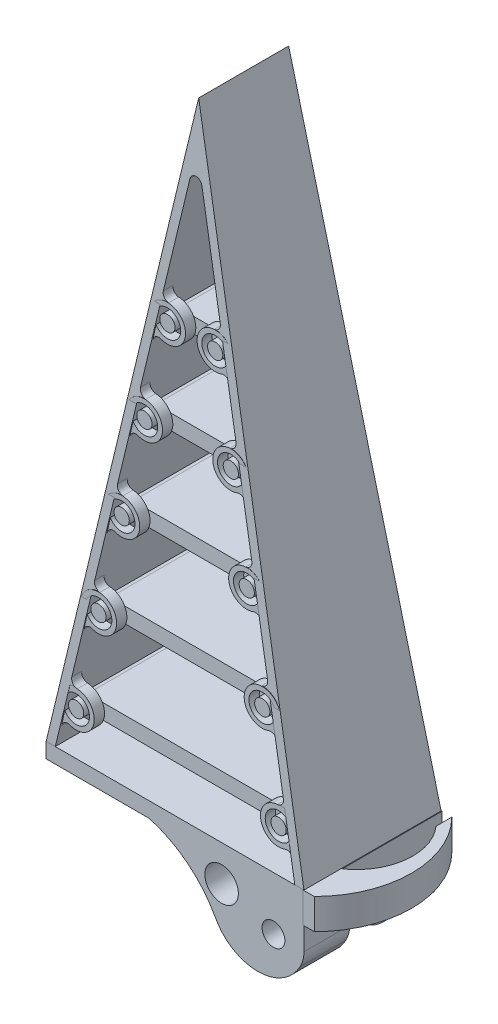
SolidWorks part; units mm, degrees
ref_plane "Ebene vorne" through (0, 0, 0) normal (0, 0, 1) x (1, 0, 0)
ref_plane "Ebene oben" through (0, 0, 0) normal (0, 1, 0) x (1, 0, 0)
ref_plane "Ebene rechts" through (0, 0, 0) normal (1, 0, 0) x (0, 0, -1)
ref_plane "Ebene7" through (0, 0, 9) normal (0, 0, 1) x (1, 0, 0)
ref_plane "Ebene8" through (17, 0, 0) normal (1, 0, 0) x (0, 0, -1)
sketch "Skizze1" plane through (0, 0, 0) normal (0, 0, 1) x (1, 0, 0)
  line L0 (0, 0) -> (16.9111, -80)
  line L1 (16.9111, -80) -> (15.7111, -80)
  line L2 (15.7111, -80) -> (0, -5.6767)
  line L3 (0, -5.6767) -> (-15.7111, -80)
  line L4 (-15.7111, -80) -> (-16.9111, -80)
  line L5 (-16.9111, -80) -> (0, 0)
  point P2 (-16.3111, -80)
  dimension "D1" = 1.2
  dimension "D2" = 1.2
  dimension "D3" = 23.872
  dimension "D4" = 80
extrude "Aufsatz-Linear austragen4" add sketch "Skizze1" along normal blind 18
sketch "Skizze11" plane through (17, 0, 0) normal (1, 0, 0) x (0, 0, -1)
  line L0 (-18, -80) -> (-14.9, 0)
  line L1 (-18, 0) -> (0, 0) construction
  line L2 (-14.9, 0) -> (-18, 0)
  line L3 (-18, 0) -> (-18, -80)
  line L4 (0, -80) -> (-3.1, 0)
  line L5 (-3.1, 0) -> (0, 0)
  line L6 (0, 0) -> (0, -80)
  dimension "D1" = 3.1
  dimension "D2" = 3.1
extrude "Schnitt-Linear austragen1" cut sketch "Skizze11" against normal through all
sketch "Skizze6" plane through (0, 0, 9) normal (0, 0, 1) x (1, 0, 0)
  line L1 (0, -5.6767) -> (-15.7111, -80) construction
  line L2 (15.7111, -80) -> (0, -5.6767) construction
  line L8 (3.1325, -25.6767) -> (-3.1325, -25.6767)
  line L11 (-3.1325, -27.6767) -> (3.1325, -27.6767)
  arc A0 (-3.1325, -25.6767) -> (-3.1325, -27.6767) centre (-3.1325, -26.6767) ccw
  arc A1 (3.1325, -25.6767) -> (3.1325, -27.6767) centre (3.1325, -26.6767) cw
  point P4 (-4.1325, -26.6767)
  point P9 (4.1325, -26.6767)
  dimension "D3" = 0.3
  dimension "D1" = 20
  dimension "D2" = 2
  dimension "D4" = 0.3
extrude "Aufsatz-Linear austragen5" add sketch "Skizze6" along normal blind 5.37 and the other way blind 5.37
sketch "Skizze7" plane through (0, 0, 9) normal (0, 0, 1) x (1, 0, 0)
  line L9 (5.6692, -37.6767) -> (-5.6692, -37.6767)
  line L12 (-5.6692, -39.6767) -> (5.6692, -39.6767)
  line L13 (-3.1325, -27.6767) -> (3.1325, -27.6767) construction
  line L14 (0, -5.6767) -> (-15.7111, -80) construction
  line L15 (15.7111, -80) -> (0, -5.6767) construction
  arc A0 (-5.6692, -37.6767) -> (-5.6692, -39.6767) centre (-5.6692, -38.6767) ccw
  arc A1 (5.6692, -37.6767) -> (5.6692, -39.6767) centre (5.6692, -38.6767) cw
  point P3 (-6.6692, -38.6767)
  point P10 (6.6692, -38.6767)
  dimension "D3" = 0.3
  dimension "D1" = 10
  dimension "D2" = 2
  dimension "D4" = 0.3
extrude "Aufsatz-Linear austragen6" add sketch "Skizze7" along normal blind 5.85 and the other way blind 5.85
sketch "Skizze8" plane through (0, 0, 9) normal (0, 0, 1) x (1, 0, 0)
  line L9 (8.2059, -49.6767) -> (-8.2059, -49.6767)
  line L12 (-8.2059, -51.6767) -> (8.2059, -51.6767)
  line L13 (-5.6692, -39.6767) -> (5.6692, -39.6767) construction
  line L14 (0, -5.6767) -> (-15.7111, -80) construction
  line L15 (15.7111, -80) -> (0, -5.6767) construction
  arc A0 (-8.2059, -49.6767) -> (-8.2059, -51.6767) centre (-8.2059, -50.6767) ccw
  arc A1 (8.2059, -49.6767) -> (8.2059, -51.6767) centre (8.2059, -50.6767) cw
  point P6 (-9.2059, -50.6767)
  point P11 (9.2059, -50.6767)
  dimension "D3" = 0.3
  dimension "D1" = 10
  dimension "D2" = 2
  dimension "D4" = 0.3
extrude "Aufsatz-Linear austragen7" add sketch "Skizze8" along normal blind 6.3 and the other way blind 6.3
sketch "Skizze9" plane through (0, 0, 9) normal (0, 0, 1) x (1, 0, 0)
  line L9 (10.7426, -61.6767) -> (-10.7426, -61.6767)
  line L12 (-10.7426, -63.6767) -> (10.7426, -63.6767)
  line L13 (-8.2059, -51.6767) -> (8.2059, -51.6767) construction
  line L14 (0, -5.6767) -> (-15.7111, -80) construction
  line L15 (15.7111, -80) -> (0, -5.6767) construction
  arc A0 (-10.7426, -61.6767) -> (-10.7426, -63.6767) centre (-10.7426, -62.6767) ccw
  arc A1 (10.7426, -61.6767) -> (10.7426, -63.6767) centre (10.7426, -62.6767) cw
  point P3 (-11.7426, -62.6767)
  point P10 (11.7426, -62.6767)
  dimension "D3" = 0.3
  dimension "D1" = 10
  dimension "D2" = 2
  dimension "D4" = 0.3
extrude "Aufsatz-Linear austragen8" add sketch "Skizze9" along normal blind 6.8 and the other way blind 6.8
sketch "Skizze10" plane through (0, 0, 9) normal (0, 0, 1) x (1, 0, 0)
  line L9 (13.2792, -73.6767) -> (-13.2792, -73.6767)
  line L12 (-13.2792, -75.6767) -> (13.2792, -75.6767)
  line L13 (-10.7426, -63.6767) -> (10.7426, -63.6767) construction
  line L14 (0, -5.6767) -> (-15.7111, -80) construction
  line L15 (15.7111, -80) -> (0, -5.6767) construction
  arc A0 (-13.2792, -73.6767) -> (-13.2792, -75.6767) centre (-13.2792, -74.6767) ccw
  arc A1 (13.2792, -73.6767) -> (13.2792, -75.6767) centre (13.2792, -74.6767) cw
  point P3 (-14.2792, -74.6767)
  point P10 (14.2792, -74.6767)
  dimension "D3" = 0.3
  dimension "D1" = 10
  dimension "D2" = 2
  dimension "D4" = 0.3
extrude "Aufsatz-Linear austragen9" add sketch "Skizze10" along normal blind 7.2 and the other way blind 7.2
sketch "Skizze13" plane through (0, 0, 14.37) normal (0, 0, 1) x (1, 0, 0)
  circle A0 centre (-3.1325, -26.6767) radius 1
  circle A1 centre (3.1325, -26.6767) radius 1
  dimension "D1" = 2
  dimension "D2" = 2
extrude "Aufsatz-Linear austragen12" add sketch "Skizze13" along normal blind 1.5
sketch "Skizze15" plane through (0, 0, 15.3) normal (0, 0, 1) x (1, 0, 0)
  circle A0 centre (-8.2059, -50.6767) radius 1
  circle A1 centre (8.2059, -50.6767) radius 1
extrude "Aufsatz-Linear austragen14" add sketch "Skizze15" along normal blind 1.5
sketch "Skizze14" plane through (0, 0, 14.85) normal (0, 0, 1) x (1, 0, 0)
  circle A0 centre (-5.6692, -38.6767) radius 1
  circle A1 centre (5.6692, -38.6767) radius 1
extrude "Aufsatz-Linear austragen13" add sketch "Skizze14" along normal blind 1.5
sketch "Skizze16" plane through (0, 0, 15.8) normal (0, 0, 1) x (1, 0, 0)
  circle A0 centre (-10.7426, -62.6767) radius 1
  circle A1 centre (10.7426, -62.6767) radius 1
extrude "Aufsatz-Linear austragen15" add sketch "Skizze16" along normal blind 1.5
sketch "Skizze17" plane through (0, 0, 16.2) normal (0, 0, 1) x (1, 0, 0)
  circle A0 centre (-13.2792, -74.6767) radius 1
  circle A1 centre (13.2792, -74.6767) radius 1
extrude "Aufsatz-Linear austragen16" add sketch "Skizze17" along normal blind 1.5
sketch "Skizze18" plane through (0, 0, 3.63) normal (0, 0, -1) x (-1, 0, 0)
  circle A0 centre (-3.1325, -26.6767) radius 1
  circle A1 centre (3.1325, -26.6767) radius 1
extrude "Aufsatz-Linear austragen17" add sketch "Skizze18" along normal blind 1.5
sketch "Skizze19" plane through (0, 0, 3.15) normal (0, 0, -1) x (-1, 0, 0)
  circle A0 centre (-5.6692, -38.6767) radius 1
  circle A1 centre (5.6692, -38.6767) radius 1
extrude "Aufsatz-Linear austragen18" add sketch "Skizze19" along normal blind 1.5
sketch "Skizze20" plane through (0, 0, 2.7) normal (0, 0, -1) x (-1, 0, 0)
  circle A0 centre (-8.2059, -50.6767) radius 1
  circle A1 centre (8.2059, -50.6767) radius 1
extrude "Aufsatz-Linear austragen19" add sketch "Skizze20" along normal blind 1.5
sketch "Skizze21" plane through (0, 0, 2.2) normal (0, 0, -1) x (-1, 0, 0)
  circle A0 centre (-10.7426, -62.6767) radius 1
  circle A1 centre (10.7426, -62.6767) radius 1
extrude "Aufsatz-Linear austragen20" add sketch "Skizze21" along normal blind 1.5
sketch "Skizze22" plane through (0, 0, 1.8) normal (0, 0, -1) x (-1, 0, 0)
  circle A0 centre (-13.2792, -74.6767) radius 1
  circle A1 centre (13.2792, -74.6767) radius 1
extrude "Aufsatz-Linear austragen21" add sketch "Skizze22" along normal blind 1.5
sketch "Skizze24" plane through (0, 0, 15.87) normal (0, 0, 1) x (1, 0, 0)
  circle A0 centre (-3.1325, -26.6767) radius 1.75
  circle A1 centre (-3.1325, -26.6767) radius 2.375
  circle A2 centre (3.1325, -26.6767) radius 1.75
  circle A3 centre (3.1325, -26.6767) radius 2.375
  dimension "D1" = 3.5
  dimension "D2" = 4.75
  dimension "D3" = 3.5
  dimension "D4" = 4.75
extrude "Aufsatz-Linear austragen22" add sketch "Skizze24" against normal blind 1.35
sketch "Skizze25" plane through (0, 0, 16.35) normal (0, 0, 1) x (1, 0, 0)
  circle A0 centre (-5.6692, -38.6767) radius 1.75
  circle A1 centre (-5.6692, -38.6767) radius 2.375
  circle A2 centre (5.6692, -38.6767) radius 1.75
  circle A3 centre (5.6692, -38.6767) radius 2.375
  dimension "D1" = 3.5
  dimension "D2" = 4.75
  dimension "D3" = 3.5
  dimension "D4" = 4.75
extrude "Aufsatz-Linear austragen23" add sketch "Skizze25" against normal blind 1.35
sketch "Skizze26" plane through (0, 0, 16.8) normal (0, 0, 1) x (1, 0, 0)
  circle A0 centre (-8.2059, -50.6767) radius 1.75
  circle A1 centre (-8.2059, -50.6767) radius 2.375
  circle A2 centre (8.2059, -50.6767) radius 1.75
  circle A3 centre (8.2059, -50.6767) radius 2.375
  dimension "D1" = 3.5
  dimension "D2" = 4.75
  dimension "D3" = 3.5
  dimension "D4" = 4.75
extrude "Aufsatz-Linear austragen24" add sketch "Skizze26" against normal blind 1.35
sketch "Skizze27" plane through (0, 0, 17.3) normal (0, 0, 1) x (1, 0, 0)
  circle A0 centre (-10.7426, -62.6767) radius 1.75
  circle A1 centre (-10.7426, -62.6767) radius 2.375
  circle A2 centre (10.7426, -62.6767) radius 1.75
  circle A3 centre (10.7426, -62.6767) radius 2.375
  dimension "D1" = 3.5
  dimension "D2" = 4.75
  dimension "D3" = 3.5
  dimension "D4" = 4.75
extrude "Aufsatz-Linear austragen25" add sketch "Skizze27" against normal blind 1.35
sketch "Skizze28" plane through (0, 0, 17.7) normal (0, 0, 1) x (1, 0, 0)
  circle A0 centre (-13.2792, -74.6767) radius 1.75
  circle A1 centre (-13.2792, -74.6767) radius 2.375
  circle A2 centre (13.2792, -74.6767) radius 1.75
  circle A3 centre (13.2792, -74.6767) radius 2.375
  dimension "D1" = 3.5
  dimension "D2" = 4.75
  dimension "D3" = 3.5
  dimension "D4" = 4.75
extrude "Aufsatz-Linear austragen26" add sketch "Skizze28" against normal blind 1.35
sketch "Skizze29" plane through (0, 0, 2.13) normal (0, 0, -1) x (-1, 0, 0)
  circle A0 centre (-3.1325, -26.6767) radius 1.75
  circle A1 centre (-3.1325, -26.6767) radius 2.375
  circle A2 centre (3.1325, -26.6767) radius 1.75
  circle A3 centre (3.1325, -26.6767) radius 2.375
extrude "Aufsatz-Linear austragen27" add sketch "Skizze29" against normal blind 1.35
sketch "Skizze30" plane through (0, 0, 1.65) normal (0, 0, -1) x (-1, 0, 0)
  circle A0 centre (-5.6692, -38.6767) radius 1.75
  circle A1 centre (-5.6692, -38.6767) radius 2.375
  circle A2 centre (5.6692, -38.6767) radius 1.75
  circle A3 centre (5.6692, -38.6767) radius 2.375
extrude "Aufsatz-Linear austragen28" add sketch "Skizze30" against normal blind 1.35
sketch "Skizze31" plane through (0, 0, 1.2) normal (0, 0, -1) x (-1, 0, 0)
  circle A0 centre (-8.2059, -50.6767) radius 1.75
  circle A1 centre (-8.2059, -50.6767) radius 2.375
  circle A2 centre (8.2059, -50.6767) radius 1.75
  circle A3 centre (8.2059, -50.6767) radius 2.375
extrude "Aufsatz-Linear austragen29" add sketch "Skizze31" against normal blind 1.35
sketch "Skizze32" plane through (0, 0, 0.7) normal (0, 0, -1) x (-1, 0, 0)
  circle A0 centre (-10.7426, -62.6767) radius 1.75
  circle A1 centre (-10.7426, -62.6767) radius 2.375
  circle A2 centre (10.7426, -62.6767) radius 1.75
  circle A3 centre (10.7426, -62.6767) radius 2.375
extrude "Aufsatz-Linear austragen30" add sketch "Skizze32" against normal blind 1.35
sketch "Skizze33" plane through (0, 0, 0.3) normal (0, 0, -1) x (-1, 0, 0)
  circle A0 centre (-13.2792, -74.6767) radius 1.75
  circle A1 centre (-13.2792, -74.6767) radius 2.375
  circle A2 centre (13.2792, -74.6767) radius 1.75
  circle A3 centre (13.2792, -74.6767) radius 2.375
extrude "Aufsatz-Linear austragen31" add sketch "Skizze33" against normal blind 1.35
fillet "Verrundung1" radius 0.8 1 edges at (0, -5.6767, 9)
fillet "Verrundung2" radius 0.8 40 edges at (12.4073, -64.3707, 16.625) (9.8706, -52.3707, 16.125) (7.3339, -40.3707, 15.675) (4.7973, -28.3707, 15.195) (-4.7973, -28.3707, 15.195) (-7.3339, -40.3707, 15.675) (-9.8706, -52.3707, 16.125) (-12.4073, -64.3707, 16.625) (-14.9439, -76.3707, 17.025) (14.9439, -76.3707, 17.025) (14.116, -72.454, 17.025) (-14.116, -72.454, 17.025) (-11.5793, -60.454, 16.5963) (11.5793, -60.454, 16.5963) (9.0427, -48.454, 16.1138) (-9.0427, -48.454, 16.1138) (-6.506, -36.454, 15.6563) (6.506, -36.454, 15.6563) (3.9693, -24.454, 15.1838) (-3.9693, -24.454, 15.1838) (-7.3339, -40.3707, 2.325) (-4.7973, -28.3707, 2.805) (-3.9693, -24.454, 2.8162) (-6.506, -36.454, 2.3437) (-9.0427, -48.454, 1.8862) (-9.8706, -52.3707, 1.875) (-12.4073, -64.3707, 1.375) (-11.5793, -60.454, 1.4037) (-14.116, -72.454, 0.975) (-14.9439, -76.3707, 0.975) (14.9439, -76.3707, 0.975) (14.116, -72.454, 0.975) (12.4073, -64.3707, 1.375) (11.5793, -60.454, 1.4037) (9.8706, -52.3707, 1.875) (9.0427, -48.454, 1.8862) (7.3339, -40.3707, 2.325) (6.506, -36.454, 2.3437) (4.7973, -28.3707, 2.805) (3.9693, -24.454, 2.8162)
sketch "Skizze37" plane through (0, -80, 0) normal (0, -1, 0) x (1, 0, 0)
  line L0 (-16.9111, 0) -> (-15.7111, 0)
  line L1 (-15.7111, 0) -> (16.9111, 0)
  line L2 (16.9111, 0) -> (16.9111, 18)
  line L3 (16.9111, 18) -> (-16.9111, 18)
  line L4 (-16.9111, 18) -> (-16.9111, 0)
extrude "Aufsatz-Linear austragen32" add sketch "Skizze37" along normal blind 2
sketch "Skizze38" plane through (0, 0, 18) normal (0, 0, 1) x (1, 0, 0)
  line L0 (16.9111, -82) -> (6.7313, -82)
  line L1 (16.9111, -82) -> (16.9111, -87)
  line L2 (16.9111, -82) -> (-16.9111, -82) construction
  line L3 (16.9111, -82) -> (16.9111, -80) construction
  circle A0 centre (12.9111, -87) radius 4
  circle A1 centre (12.9111, -87) radius 1.5
  arc A2 (-3.3949, -82) -> (5.3134, -88.966) centre (-7.2601, -95.7582) cw
  arc A4 (5.3134, -88.966) -> (16.3947, -88.966) centre (10.8541, -85.9729) ccw
  line M6 (-16.9111, -82) -> (16.9111, -82)
  dimension "D1" = 3
  dimension "D2" = 5
  dimension "D3" = 8
extrude "Aufsatz-Linear austragen34" add sketch "Skizze38" against normal blind 18 contours A0 L1 M6 | A0 A1 region at (7.5381, -85.6971, 18) region at (16.6704, -87.9876, 18)
sketch "Skizze39" plane through (0, 0, 18) normal (0, 0, 1) x (1, 0, 0)
  circle A1 centre (12.9111, -87) radius 4
  circle A2 centre (12.9111, -87) radius 1.5 construction
extrude "Schnitt-Linear austragen2" cut sketch "Skizze39" against normal blind 6 from offset 6 offset against normal yes
sketch "Skizze40" plane through (-16.9111, 0, 0) normal (-1, 0, 0) x (0, 0, 1)
  line L7 (12, -93.7115) -> (6, -93.7115)
  line L9 (12, -93.7115) -> (12, -82)
  line L10 (18, -82) -> (0, -82) construction
  line L11 (12, -82) -> (6, -82)
  line L12 (6, -82) -> (6, -93.7115)
extrude "Schnitt-Linear austragen3" cut sketch "Skizze40" against normal blind 43.6
sketch "Skizze41" plane through (0, 0, 0) normal (0, 0, -1) x (-1, 0, 0)
  line L0 (-6.1051, -82) -> (-6.1051, -84.7) construction
  line L1 (3.3949, -82) -> (-6.1051, -82) construction
  circle A0 centre (-6.1051, -84.7) radius 2.2
  dimension "D1" = 4.4
  dimension "D2" = 2.7
  dimension "D3" = 9.5
extrude "Schnitt-Linear austragen4" cut sketch "Skizze41" against normal through all
sketch "Skizze42" plane through (-16.9111, 0, 0) normal (-1, 0, 0) x (0, 0, 1)
  line L0 (8, -82) -> (9, -82)
  line L1 (18, -82) -> (0, -82) construction
  line L3 (9, -82) -> (9, -82.5253)
  line L4 (9, -82.5253) -> (8.82, -82.5253)
  line L5 (8, -82) -> (8, -82.5253)
  line L6 (8, -82.5253) -> (8.18, -82.5253)
  line L7 (8.5, -82) -> (8.5, -82.1718) construction
  arc A0 (8.5, -82.1718) -> (8.82, -82.5253) centre (8.5, -82.4934) cw
  arc A1 (8.5, -82.1718) -> (8.18, -82.5253) centre (8.5, -82.4934) ccw
  point P16 (9, -82)
  dimension "D1" = 1
  dimension "D2" = 0.18
  dimension "D3" = 0.18
extrude "Aufsatz-Linear austragen35" add sketch "Skizze42" against normal blind 25
sketch "Skizze44" plane through (-0.4655, -82, 0) normal (0, -1, 0) x (1, 0, 0)
  line L0 (17.2655, 18.0457) -> (18.7779, 18.0457)
  line L1 (17.2655, 0) -> (18.7779, 0)
  line L2 (17.2655, 18.0457) -> (17.2655, 0)
  arc A0 (18.7779, 18.0457) -> (18.7779, 0) centre (9.7551, 9.0229) cw
extrude "Aufsatz-Linear austragen37" add sketch "Skizze44" along normal blind 2 and the other way blind 2 separate body
sketch "Skizze45" plane through (0, -84, 0) normal (0, -1, 0) x (1, 0, 0)
  line L0 (18.3124, 0) -> (17.0079, 0)
  line L1 (16.8, 0) -> (18.3124, 0) construction
  line L2 (17.0079, 0) -> (17.0079, 1.8192)
  line L3 (17.0079, 1.8192) -> (17.0079, 6.0081)
  line L4 (17.0079, 6.0081) -> (17.0079, 13.0766)
  line L5 (18.3124, 2.0795) -> (18.3124, 0)
  arc A0 (17.0079, 13.0766) -> (18.3124, 2.0795) centre (12.791, 7.0005) cw
  point P10 (16.957, 12.8618)
  point P11 (17.0079, 13.0766)
extrude "Schnitt-Linear austragen5" cut sketch "Skizze45" against normal blind 4 contours A0 L5 L0 L2 L3 L4
